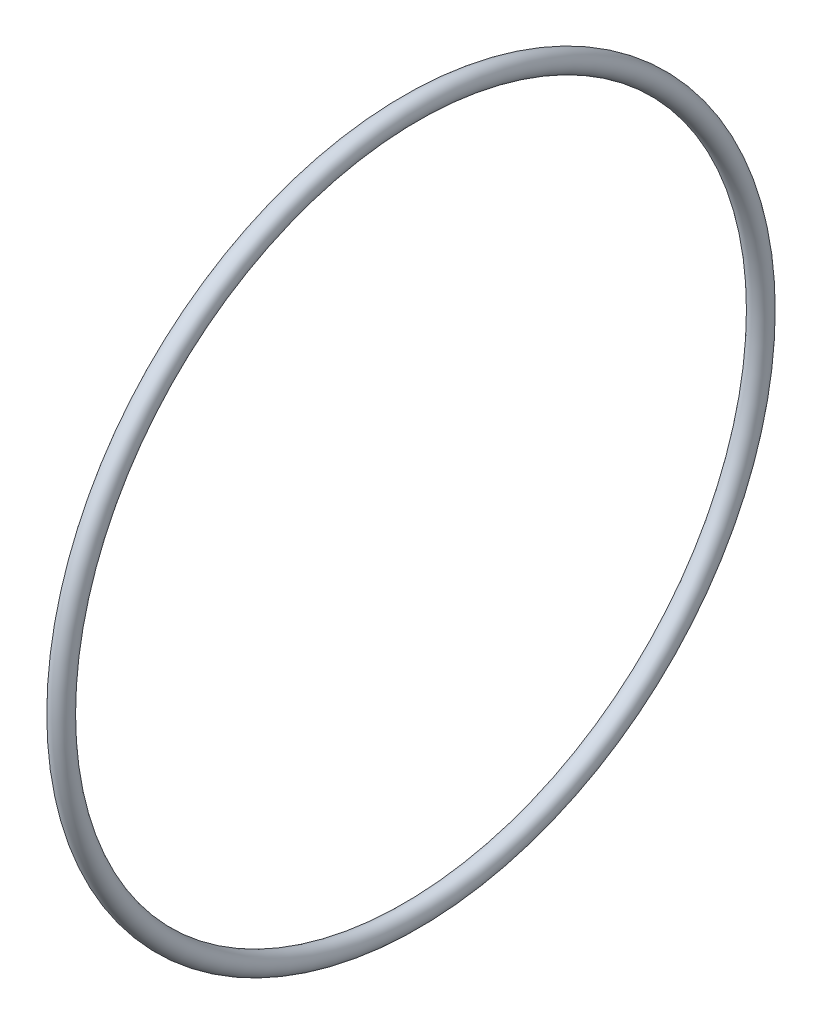
SolidWorks part; units mm, degrees
ref_plane "Front Plane" through (0, 0, 0) normal (0, 0, 1) x (1, 0, 0)
ref_plane "Top Plane" through (0, 0, 0) normal (0, 1, 0) x (1, 0, 0)
ref_plane "Right Plane" through (0, 0, 0) normal (1, 0, 0) x (0, 0, -1)
sketch "Sketch2" plane through (0, 0, 0) normal (0, 0, 1) x (1, 0, 0)
  line L0 (0, 0) -> (58.591, 0) construction
  line L2 (0, 0) -> (18.4, 0)
  line L3 (0, 0) -> (0, 2.5)
  line L4 (0, 2.5) -> (18.4, 2.5)
  line L5 (18.4, 0) -> (18.4, 2.5)
  line L6 (6, 2.5) -> (6, 6)
  line L11 (6, 6) -> (9.97, 6)
  line L16 (12.97, 6) -> (12.97, 3)
  line L17 (12.97, 3) -> (13.6304, 3)
  line L18 (13.6304, 3) -> (13.6304, 2.5)
  line L19 (13.6304, 2.5) -> (6, 2.5)
  line L22 (13.6304, 2.5) -> (16.1104, 2.5)
  line L23 (13.6304, 2.5) -> (13.6304, 4)
  line L24 (13.6304, 4) -> (16.1104, 4)
  line L25 (16.1104, 2.5) -> (16.1104, 4)
  line L27 (6, 6) -> (9.97, 6)
  line L28 (6, 6) -> (6, 9)
  line L29 (6, 9) -> (9.97, 9)
  line L30 (9.97, 6) -> (9.97, 9)
  line L31 (6, 9) -> (6, 8.25)
  line L32 (6, 8.25) -> (5, 8.25)
  line L33 (8.58, 22.001) -> (8.58, 12.476) construction
  line L34 (5, 12.476) -> (12.16, 12.476)
  line L35 (9.97, 9) -> (12.16, 9)
  line L36 (5, 7.5) -> (3, 7.5)
  line L37 (5, 8.25) -> (5, 12.476)
  line L38 (5, 7.5) -> (5, 14)
  line L39 (5, 14) -> (3, 14)
  line L40 (3, 7.5) -> (3, 14)
  line L41 (5, 22.001) -> (12.16, 22.001)
  line L42 (5, 22.001) -> (5, 30.1625)
  line L43 (5, 30.1625) -> (12.16, 30.1625)
  line L44 (12.16, 22.001) -> (12.16, 30.1625)
  line L49 (16.6304, 22.001) -> (16.6304, 7.5)
  line L51 (23.0104, 7.5) -> (23.0104, 6.5)
  line L54 (16.1104, 4) -> (13.6304, 4)
  line L56 (18.0304, 7.5) -> (23.0104, 7.5)
  line L57 (13.16, 22.001) -> (16.6304, 22.001)
  line L58 (16.1104, 3.5) -> (20.0104, 3.5)
  line L59 (29.9004, 14) -> (26.9004, 11)
  line L60 (4, 31.75) -> (18.0304, 31.75)
  line L61 (18.0304, 7.5) -> (23.0104, 7.5)
  line L62 (18.0304, 7.5) -> (18.0304, 12)
  line L63 (18.0304, 12) -> (23.0104, 12)
  line L64 (23.0104, 7.5) -> (23.0104, 12)
  line L65 (18.0304, 31.75) -> (18.0304, 12)
  line L66 (23.0104, 11) -> (26.9004, 11)
  line L67 (34.8004, 23) -> (31.3004, 19.5)
  line L68 (35.8004, 31) -> (38.7904, 33.99)
  line L69 (29.9004, 14) -> (29.9004, 15)
  line L70 (29.9004, 15) -> (22.9304, 15)
  line L71 (22.9304, 15) -> (21.0304, 15)
  line L72 (18.0304, 7.5) -> (16.6304, 7.5)
  line L73 (21.0304, 15) -> (21.0304, 43)
  line L74 (20.0304, 40) -> (10.0704, 40)
  line L75 (10.0704, 40) -> (4, 40)
  line L76 (21.0304, 43) -> (20.0304, 43)
  line L77 (22.9304, 15) -> (29.9004, 15)
  line L78 (22.9304, 15) -> (22.9304, 21)
  line L79 (22.9304, 21) -> (29.9004, 21)
  line L80 (29.9004, 15) -> (29.9004, 21)
  line L81 (10.0704, 40) -> (20.0304, 40)
  line L82 (10.0704, 40) -> (10.0704, 50)
  line L83 (10.0704, 50) -> (20.0304, 50)
  line L84 (20.0304, 40) -> (20.0304, 50)
  line L85 (4, 40) -> (4, 31.75)
  line L86 (12.97, 3) -> (12.97, 2.5)
  line L87 (31.3004, 19.5) -> (29.9004, 19.5)
  line L88 (21.51, 63.5) -> (21.51, 44)
  line L89 (21.51, 63.5) -> (25.9304, 63.5)
  line L90 (25.9304, 63.5) -> (25.9304, 25)
  line L91 (27.8304, 25) -> (25.9304, 25)
  line L92 (10.0704, 48) -> (9, 48)
  line L93 (9, 48) -> (9, 53.476)
  line L94 (9, 53.476) -> (20.0304, 53.476)
  line L95 (20.0304, 53.476) -> (20.0304, 50)
  line L96 (14.5152, 63.001) -> (14.5152, 53.476) construction
  line L97 (9, 63.001) -> (20.0304, 63.001)
  line L98 (9, 63.001) -> (9, 68.2625)
  line L99 (9, 68.2625) -> (20.0304, 68.2625)
  line L100 (20.0304, 63.001) -> (20.0304, 68.2625)
  line L101 (12.97, 6) -> (11.97, 6)
  line L102 (9, 42.5) -> (5, 42.5)
  line L103 (9, 42.5) -> (9, 55)
  line L104 (9, 55) -> (5, 55)
  line L105 (5, 42.5) -> (5, 55)
  line L106 (9.97, 6) -> (10.87, 6)
  line L107 (27.8304, 25) -> (34.8004, 25)
  line L108 (34.8004, 25) -> (34.8004, 23)
  line L109 (0, 0) -> (-2, 0)
  line L110 (0, 0) -> (0, 11)
  line L111 (27.8304, 25) -> (34.8004, 25)
  line L112 (27.8304, 25) -> (27.8304, 32.5)
  line L113 (27.8304, 32.5) -> (34.8004, 32.5)
  line L114 (34.8004, 25) -> (34.8004, 32.5)
  line L115 (35.8004, 31) -> (34.8004, 31)
  line L116 (27.8304, 32.5) -> (27.8304, 64.5)
  line L117 (21.1827, 74.025) -> (6.8477, 74.025)
  line L118 (6.8477, 74.025) -> (6.8477, 76.2)
  line L119 (38.7904, 47.29) -> (30.8304, 55.25)
  line L120 (0, 11) -> (-2, 11)
  line L121 (38.7904, 43.815) -> (30.8529, 43.815)
  line L123 (-4.8, 69.85) -> (1.55, 76.2)
  line L124 (38.7904, 47.29) -> (38.7904, 33.99)
  line L125 (-2, 0) -> (-2, 11)
  line L126 (38.7904, 37.465) -> (30.8529, 37.465)
  line L127 (30.8529, 43.815) -> (30.8529, 37.465)
  line L128 (6, 2.5) -> (6, 0)
  line L129 (0, 63.5) -> (0, 30)
  line L132 (5, 63.5) -> (0, 63.5)
  line L136 (-1.8, 30) -> (-11.76, 30)
  line L138 (-13.76, 25.4) -> (-2, 25.4)
  line L139 (-2, 25.4) -> (-2, 11.5)
  line L140 (27.8304, 64.5) -> (21.1827, 64.5)
  line L141 (-1.8, 30) -> (-11.76, 30)
  line L142 (-1.8, 30) -> (-1.8, 39)
  line L143 (-1.8, 39) -> (-11.76, 39)
  line L144 (-11.76, 30) -> (-11.76, 39)
  line L145 (21.1827, 64.5) -> (21.1827, 74.025)
  line L146 (-12.76, 37) -> (-12.76, 47.29)
  line L147 (-12.76, 37) -> (-11.76, 37)
  line L148 (30.8304, 55.25) -> (30.8304, 76.2)
  line L149 (11.97, 6) -> (11.97, 5.45)
  line L154 (-2, 11.5) -> (1, 11.5)
  line L155 (5, 60.6197) -> (24.05, 60.6197)
  line L160 (5, 60.6197) -> (5, 55.8572)
  line L161 (5, 55.8572) -> (24.05, 55.8572)
  line L166 (24.05, 60.6197) -> (24.05, 55.8572)
  line L167 (5, 60.6197) -> (24.05, 55.8572) construction
  line L172 (5, 55.8572) -> (24.05, 60.6197) construction
  line L173 (24.05, 62.2072) -> (25.9304, 62.2072)
  line L174 (11.97, 5.45) -> (10.87, 5.45)
  line L175 (10.87, 6) -> (10.87, 5.45)
  line L176 (24.05, 62.2072) -> (24.05, 54.2697)
  line L177 (24.05, 54.2697) -> (25.9304, 54.2697)
  line L178 (25.9304, 62.2072) -> (25.9304, 54.2697)
  line L179 (24.05, 62.2072) -> (25.9304, 54.2697) construction
  line L180 (24.05, 54.2697) -> (25.9304, 62.2072) construction
  line L181 (3, 19.6197) -> (15.7, 19.6197)
  line L182 (3, 19.6197) -> (3, 14.8572)
  line L183 (3, 14.8572) -> (15.7, 14.8572)
  line L184 (15.7, 19.6197) -> (15.7, 14.8572)
  line L185 (3, 19.6197) -> (15.7, 14.8572) construction
  line L186 (3, 14.8572) -> (15.7, 19.6197) construction
  line L187 (15.7, 21.2072) -> (16.6304, 21.2072)
  line L188 (15.7, 21.2072) -> (15.7, 13.2697)
  line L189 (15.7, 13.2697) -> (16.6304, 13.2697)
  line L190 (16.6304, 21.2072) -> (16.6304, 13.2697)
  line L191 (15.7, 21.2072) -> (16.6304, 13.2697) construction
  line L192 (15.7, 13.2697) -> (16.6304, 21.2072) construction
  line L193 (1, 11.5) -> (1, 6.5)
  line L194 (1, 6.5) -> (3, 6.5)
  line L195 (23.0104, 6.5) -> (20.0104, 3.5)
  line L196 (5, 63.5) -> (5, 42.5)
  line L197 (5, 42.5) -> (3, 42.5)
  line L198 (3, 42.5) -> (3, 6.5)
  line L199 (6, 0) -> (12.97, 0)
  line L200 (12.97, 0) -> (12.97, 2.5)
  line L201 (18.0304, 31.75) -> (18.0304, 35.875)
  line L202 (18.0304, 35.875) -> (21.0304, 35.875)
  line L203 (30.8304, 76.2) -> (6.8477, 76.2)
  line L204 (3.4027, 69.85) -> (7.8477, 69.85) construction
  line L205 (7.8477, 67.4687) -> (26.8977, 67.4688)
  line L206 (7.8477, 74.025) -> (7.8477, 64.5)
  line L207 (7.8477, 64.5) -> (-1.8, 64.5)
  line L208 (-1.8, 64.5) -> (-1.8, 39)
  line L209 (-12.76, 47.29) -> (-4.8, 55.25)
  line L210 (-4.8, 55.25) -> (-4.8, 69.85)
  line L211 (7.8477, 67.4687) -> (7.8477, 72.2313)
  line L212 (7.8477, 72.2313) -> (26.8977, 72.2313)
  line L213 (26.8977, 67.4688) -> (26.8977, 72.2313)
  line L214 (26.8977, 73.8187) -> (30.8304, 73.8187)
  line L215 (26.8977, 73.8187) -> (26.8977, 65.8813)
  line L216 (26.8977, 65.8813) -> (30.8304, 65.8813)
  line L217 (30.8304, 73.8187) -> (30.8304, 65.8813)
  line L218 (3.4027, 72.2313) -> (25.6277, 72.2313)
  line L219 (3.4027, 72.2313) -> (3.4027, 67.4687)
  line L220 (3.4027, 67.4687) -> (25.6277, 67.4687)
  line L221 (25.6277, 72.2313) -> (25.6277, 67.4687)
  line L222 (25.6277, 69.85) -> (21.1827, 69.85) construction
  line L223 (21.51, 44) -> (22.9304, 44)
  line L224 (22.9304, 44) -> (22.9304, 21)
  line L225 (13.6304, 4) -> (13.6304, 12.2697)
  line L226 (13.6304, 12.2697) -> (13.16, 12.2697)
  line L227 (13.16, 12.2697) -> (13.16, 22.001)
  line L228 (12.16, 9) -> (12.16, 12.476)
  line L229 (-1.8, 30) -> (0, 30)
  line L230 (9, 65.6317) -> (3.4027, 65.6317) construction
  line L231 (20.0304, 65.6317) -> (25.6277, 65.6317) construction
  line L232 (1.55, 76.2) -> (6.8477, 76.2)
  line L233 (-11.76, 30) -> (-13.76, 30)
  line L234 (-13.76, 30) -> (-13.76, 25.4)
  circle A0 centre (26.8804, 25.95) radius 0.95
  circle A1 centre (21.9804, 15.95) radius 0.95
  circle A2 centre (17.3304, 8.2) radius 0.7
  circle A3 centre (10.42, 6.45) radius 0.45
  circle A4 centre (-0.9, 30.9) radius 0.9
  point P7 (24.9902, 58.2385)
  point P131 (16.1652, 17.2385)
  point P135 (14.525, 58.2385)
  point P146 (9.35, 17.2385)
sketch "Sketch3" plane through (0, 0, 0) normal (0, 0, 1) x (1, 0, 0)
  circle A0 centre (-0.9, 30.9) radius 0.9 construction
  circle A1 centre (-0.9, 30.9) radius 0.9
revolve "Revolve1" add sketch "Sketch3" angle 360 about L0
